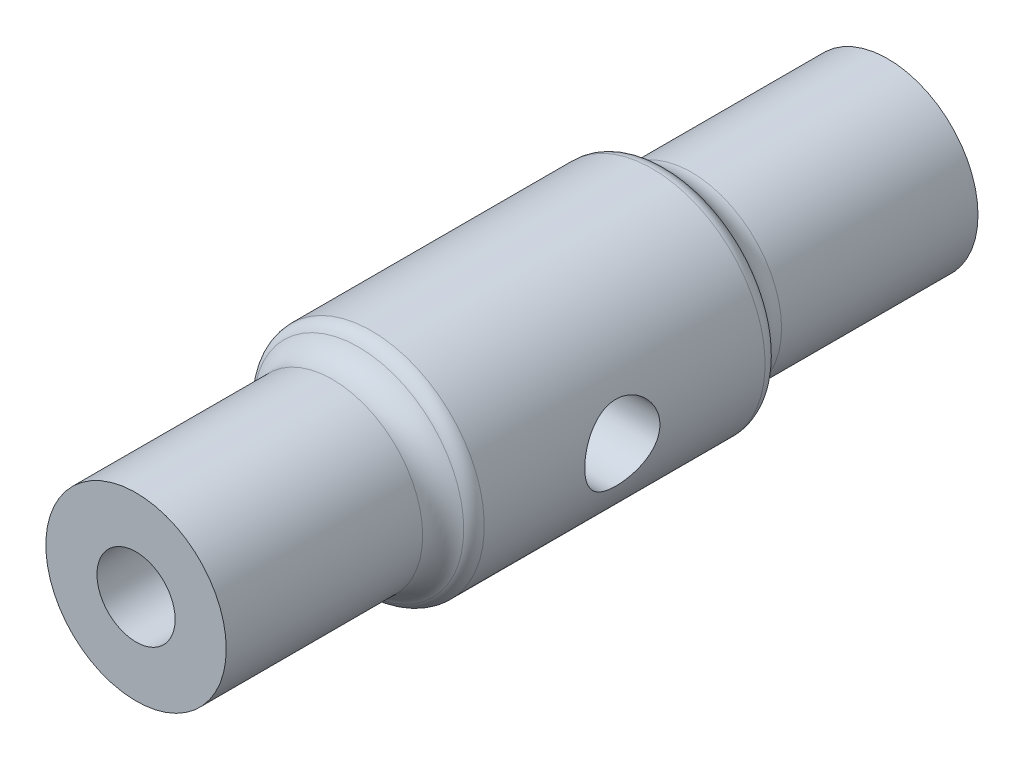
SolidWorks part; units mm, degrees
ref_plane "Front Plane" through (0, 0, 0) normal (0, 0, 1) x (1, 0, 0)
ref_plane "Top Plane" through (0, 0, 0) normal (0, 1, 0) x (1, 0, 0)
ref_plane "Right Plane" through (0, 0, 0) normal (1, 0, 0) x (0, 0, -1)
sketch "Sketch1" plane through (0, 0, 0) normal (0, 0, 1) x (1, 0, 0)
  circle A0 centre (0, 0) radius 6
  dimension "D1" = 12
extrude "Boss-Extrude1" add sketch "Sketch1" along normal mid plane 15
sketch "Sketch2" plane through (0, 0, 7.5) normal (0, 0, 1) x (1, 0, 0)
  circle A0 centre (0, 0) radius 7.5
  dimension "D1" = 15
extrude "Boss-Extrude2" add sketch "Sketch2" along normal blind 20
ref_plane "Plane1" through (0, 0, 17.5) normal (0, 0, 1) x (1, 0, 0)
mirror "Mirror1" about plane through (0, 0, 17.5) normal (0, 0, 1) of "Boss-Extrude1"
sketch "Sketch3" plane through (0, 0, -7.5) normal (0, 0, -1) x (-1, 0, 0)
  circle A0 centre (0, 0) radius 3.1
  dimension "D1" = 6.2
extrude "Cut-Extrude1" cut sketch "Sketch3" against normal blind 15
sketch "Sketch4" plane through (0, 0, 0) normal (1, 0, 0) x (0, 0, -1)
  circle A0 centre (-17.6555, 0) radius 2.5
  dimension "D1" = 5
extrude "Cut-Extrude2" cut sketch "Sketch4" against normal mid plane 22
sketch "Sketch6" plane through (0, 0, 0) normal (0, 1, 0) x (1, 0, 0)
  line L0 (0, -11.5) -> (0, -23.5) construction
  line L1 (3, -11.5) -> (3, -23.5)
  line L2 (-3, -11.5) -> (-3, -23.5)
  line L3 (2.0318, -17.5) -> (-2.7148, -17.5) construction
  line L4 (-8.25, -17.5) -> (8.25, -17.5) construction
  line L5 (0, -7.5) -> (0, -27.5) construction
  line L6 (7.5, -7.5) -> (-7.5, -7.5) construction
  line L7 (-6, -27.5) -> (6, -27.5) construction
  line L8 (-7.5, -20.5503) -> (-7.5, -14.4497) construction
  line L9 (-7.5, -20.1555) -> (-7.5, -27.5) construction
  line L10 (-7.5, -17.5) -> (7.7072, -17.5) construction
  line L11 (-3, -17.5) -> (15.1479, -17.5) construction
  arc A0 (3, -11.5) -> (-3, -11.5) centre (0, -11.5) ccw
  arc A1 (-3, -23.5) -> (3, -23.5) centre (0, -23.5) ccw
  point P3 (0, -17.5)
  dimension "D2" = 3
  dimension "D3" = 4
  dimension "D1" = 12
extrude "Cut-Extrude3" cut sketch "Sketch6" against normal blind 20
fillet "Fillet1" radius 2 2 edges at (6, 0, 27.5) (6, 0, 7.5)
fillet "Fillet2" radius 1 2 edges at (7.5, 0, 27.5) (7.5, 0, 7.5)
sketch "Sketch7" plane through (0, 0, 42.5) normal (0, 0, 1) x (1, 0, 0)
  circle A0 centre (0, 0) radius 2.6
  dimension "D1" = 5.2
extrude "Cut-Extrude4" cut sketch "Sketch7" against normal blind 15
sketch "Sketch8" plane through (0, 0, 0) normal (0, -1, 0) x (1, 0, 0)
  line L0 (-3, 20.1555) -> (-3, 23.5)
  line L1 (-3, 23.5) -> (-3, 15.1555)
  line L2 (-3, 15.1555) -> (-3, 11.5)
  line L3 (3, 23.5) -> (3, 20.1555)
  line L4 (3, 20.1555) -> (3, 15.1555)
  line L5 (3, 15.1555) -> (3, 11.5)
  arc A0 (-3, 11.5) -> (3, 11.5) centre (0, 11.5) ccw construction
  arc A1 (-3, 11.5) -> (3, 11.5) centre (0, 11.5) ccw
  arc A2 (3, 23.5) -> (-3, 23.5) centre (0, 23.5) ccw
  arc A3 (3, 23.5) -> (-3, 23.5) centre (0, 23.5) ccw construction
  line M1 (3, 20.1555) -> (3, 23.5)
  arc M2 (3, 23.5) -> (-3, 23.5) centre (0, 23.5) ccw
  line M3 (-3, 23.5) -> (-3, 20.1555)
  line M4 (-3, 20.1555) -> (3, 20.1555)
extrude "Cut-Extrude5" cut sketch "Sketch8" against normal blind 6 contours L2 A1 L5 L4 L1 M4 | M4 M1 M2 M3 region at (0, 0, 14.6293) region at (0, 0, 23.0452)
